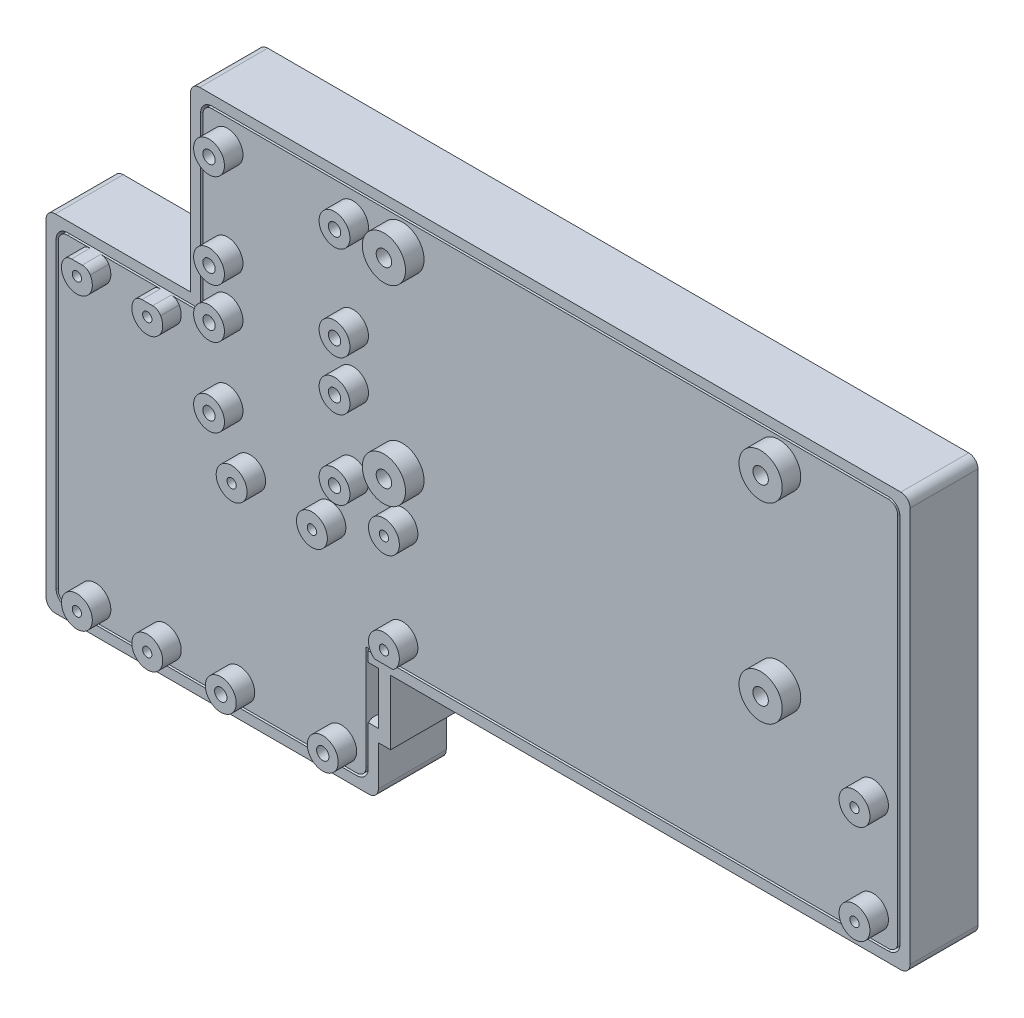
SolidWorks part; units mm, degrees
ref_plane "Front Plane" through (0, 0, 0) normal (0, 0, 1) x (1, 0, 0)
ref_plane "Top Plane" through (0, 0, 0) normal (0, 1, 0) x (1, 0, 0)
ref_plane "Right Plane" through (0, 0, 0) normal (1, 0, 0) x (0, 0, -1)
sketch "Sketch1" plane through (0, 0, 0) normal (0, 0, 1) x (1, 0, 0)
  line L0 (0, -14.35) -> (0, -44.85) construction
  line L1 (-8.255, -44.85) -> (8.255, -44.85) construction
  line L2 (-8.255, -44.85) -> (-8.255, -14.35) construction
  line L3 (-8.255, -14.35) -> (8.255, -14.35) construction
  line L4 (8.255, -44.85) -> (8.255, -14.35) construction
  line L5 (-8.255, -44.85) -> (8.255, -14.35) construction
  line L6 (-8.255, -14.35) -> (8.255, -44.85) construction
  line L7 (-10.16, 6.35) -> (10.16, 6.35) construction
  line L8 (-10.16, 6.35) -> (-10.16, -6.35) construction
  line L9 (-10.16, -6.35) -> (10.16, -6.35) construction
  line L10 (10.16, 6.35) -> (10.16, -6.35) construction
  line L11 (-10.16, 6.35) -> (10.16, -6.35) construction
  line L12 (-10.16, -6.35) -> (10.16, 6.35) construction
  line L13 (-10.16, 29.59) -> (10.16, 29.59) construction
  line L14 (-10.16, 29.59) -> (-10.16, 14.35) construction
  line L15 (-10.16, 14.35) -> (10.16, 14.35) construction
  line L16 (10.16, 29.59) -> (10.16, 14.35) construction
  line L17 (-10.16, 29.59) -> (10.16, 14.35) construction
  line L18 (-10.16, 14.35) -> (10.16, 29.59) construction
  line L19 (-20.16, 2.15) -> (-31.56, 2.15) construction
  line L20 (-20.16, 2.15) -> (-20.16, -44.85) construction
  line L21 (-20.16, -44.85) -> (-31.56, -44.85) construction
  line L22 (-31.56, 2.15) -> (-31.56, -44.85) construction
  line L23 (-20.16, 2.15) -> (-31.56, -44.85) construction
  line L24 (-20.16, -44.85) -> (-31.56, 2.15) construction
  line L25 (18.16, 29.59) -> (79.16, 29.59) construction
  line L26 (18.16, 29.59) -> (18.16, -1.41) construction
  line L27 (18.16, -1.41) -> (79.16, -1.41) construction
  line L28 (79.16, 29.59) -> (79.16, -1.41) construction
  line L29 (18.16, 29.59) -> (79.16, -1.41) construction
  line L30 (18.16, -1.41) -> (79.16, 29.59) construction
  line L31 (18.16, -9.41) -> (94.36, -9.41) construction
  line L32 (18.16, -9.41) -> (18.16, -25.41) construction
  line L33 (18.16, -25.41) -> (94.36, -25.41) construction
  line L34 (94.36, -9.41) -> (94.36, -25.41) construction
  line L35 (18.16, -9.41) -> (94.36, -25.41) construction
  line L36 (18.16, -25.41) -> (94.36, -9.41) construction
  line L37 (-37.56, 4.15) -> (-37.56, -47.85)
  line L38 (-37.56, -47.85) -> (12.255, -47.85)
  line L39 (12.255, -47.85) -> (12.255, -29.41)
  line L40 (12.255, -29.41) -> (98.36, -29.41)
  line L41 (98.36, -29.41) -> (98.36, 33.59)
  line L42 (98.36, 33.59) -> (-14.16, 33.59)
  line L43 (-14.16, 33.59) -> (-14.16, 4.15)
  line L44 (-14.16, 4.15) -> (-37.56, 4.15)
  line L45 (-39.56, 6.15) -> (-39.56, -49.85)
  line L46 (-39.56, -49.85) -> (14.255, -49.85)
  line L47 (14.255, -49.85) -> (14.255, -31.41)
  line L48 (14.255, -31.41) -> (100.36, -31.41)
  line L49 (100.36, -31.41) -> (100.36, 35.59)
  line L50 (100.36, 35.59) -> (-16.16, 35.59)
  line L51 (-16.16, 35.59) -> (-16.16, 6.15)
  line L52 (-16.16, 6.15) -> (-39.56, 6.15)
  line L53 (-35.56, 2.15) -> (-35.56, -45.85)
  line L54 (16.255, -31.41) -> (16.255, -41.85)
  line L55 (16.255, -41.85) -> (12.255, -41.85)
  line L56 (12.255, -39.85) -> (14.255, -39.85)
  line L57 (14.255, -31.41) -> (12.255, -31.41)
  line L58 (-35.56, -45.85) -> (10.255, -45.85)
  line L59 (13.255, -39.85) -> (13.255, -41.85) construction
  line L60 (10.255, -45.85) -> (10.255, -27.41)
  line L61 (10.255, -27.41) -> (96.36, -27.41)
  line L62 (96.36, -27.41) -> (96.36, 31.59)
  line L63 (96.36, 31.59) -> (-12.16, 31.59)
  line L64 (-12.16, 31.59) -> (-12.16, 2.15)
  line L65 (-12.16, 2.15) -> (-35.56, 2.15)
  line L66 (12.255, -39.85) -> (10.255, -39.85)
  line L67 (12.255, -31.41) -> (10.255, -31.41)
  circle A0 centre (-31.56, 2.15) radius 0.75
  circle A1 centre (-20.16, 2.15) radius 0.75
  circle A2 centre (-31.56, -44.85) radius 0.75
  circle A3 centre (-20.16, -44.85) radius 0.75
  circle A4 centre (-8.255, -44.85) radius 1
  circle A5 centre (8.255, -44.85) radius 1
  circle A8 centre (18.16, -25.41) radius 0.75
  circle A9 centre (18.16, -9.41) radius 0.75
  circle A10 centre (94.36, -9.41) radius 0.75
  circle A11 centre (94.36, -25.41) radius 0.75
  circle A12 centre (10.16, -6.35) radius 1
  circle A13 centre (-10.16, -6.35) radius 1
  circle A14 centre (-10.16, 6.35) radius 1
  circle A15 centre (10.16, 6.35) radius 1
  circle A16 centre (10.16, 14.35) radius 1
  circle A17 centre (10.16, 29.59) radius 1
  circle A18 centre (-10.16, 29.59) radius 1
  circle A19 centre (-10.16, 14.35) radius 1
  circle A20 centre (18.16, 29.59) radius 1.25
  circle A21 centre (18.16, -1.41) radius 1.25
  circle A22 centre (79.16, -1.41) radius 1.25
  circle A23 centre (79.16, 29.59) radius 1.25
  circle A24 centre (-6.5, -14.35) radius 0.75
  circle A25 centre (6.5, -14.35) radius 0.75
  circle A26 centre (8.255, -44.85) radius 2.5
  circle A27 centre (-8.255, -44.85) radius 2.5
  circle A28 centre (-6.5, -14.35) radius 2.5
  circle A29 centre (6.5, -14.35) radius 2.5
  circle A30 centre (10.16, -6.35) radius 2.5
  circle A31 centre (-10.16, -6.35) radius 2.5
  circle A32 centre (-10.16, 6.35) radius 2.5
  circle A33 centre (10.16, 6.35) radius 2.5
  circle A34 centre (-10.16, 14.35) radius 2.5
  circle A35 centre (10.16, 14.35) radius 2.5
  circle A36 centre (10.16, 29.59) radius 2.5
  circle A37 centre (-10.16, 29.59) radius 2.5
  circle A38 centre (-31.56, 2.15) radius 2.5
  circle A39 centre (-20.16, 2.15) radius 2.5
  circle A40 centre (-31.56, -44.85) radius 2.5
  circle A41 centre (-20.16, -44.85) radius 2.5
  circle A42 centre (18.16, 29.59) radius 3.5
  circle A43 centre (18.16, -1.41) radius 3.5
  circle A44 centre (79.16, 29.59) radius 3.5
  circle A45 centre (79.16, -1.41) radius 3.5
  circle A46 centre (18.16, -25.41) radius 2.5
  circle A47 centre (18.16, -9.41) radius 2.5
  circle A48 centre (94.36, -25.41) radius 2.5
  circle A49 centre (94.36, -9.41) radius 2.5
  point P0 (0, -29.6)
  point P5 (0, 0)
  point P10 (0, 21.97)
  point P15 (-25.86, -21.35)
  point P20 (48.66, 14.09)
  point P25 (56.26, -17.41)
  dimension "D4" = 2
  dimension "D9" = 1.5
  dimension "D21" = 2.5
  dimension "D30" = 5
  dimension "D31" = 5
  dimension "D32" = 7
  dimension "D33" = 5
  dimension "D1" = 16.51
  dimension "D2" = 20.32
  dimension "D3" = 12.7
  dimension "D5" = 15.24
  dimension "D6" = 20.32
  dimension "D7" = 47
  dimension "D8" = 11.4
  dimension "D10" = 13
  dimension "D11" = 30.5
  dimension "D12" = 16
  dimension "D13" = 76.2
  dimension "D14" = 31
  dimension "D15" = 61
  dimension "D16" = 8
  dimension "D17" = 8
  dimension "D18" = 8
  dimension "D19" = 8
  dimension "D20" = 10
  dimension "D22" = 6
  dimension "D23" = 2
  dimension "D24" = 4
  dimension "D25" = 4
  dimension "D26" = 4
  dimension "D27" = 4
  dimension "D28" = 4
  dimension "D29" = 3
  dimension "D35" = 2
  dimension "D36" = 6
  dimension "D34" = 2
  dimension "D37" = 2
extrude "base" add sketch "Sketch1" along normal blind 2 contours A49 L62 L63 A44 A42 A36 A37 L64 A34 A32 L65 A39 A38 L53 L58 A40 A41 A27 A26 L60 L61 A46 A48 A47 A45 A43 A35 A33 A31 A30 | A49 L62 A48 L61 A46 L60 L67 L39 L40 L41 L42 L43 L44 A39 L65 L64 A32 A34 A37 L63 A36 A42 A44 | A39 L44 A38 L65 | A41 L58 A40 L53 L65 A38 L44 L37 L38 L39 L66 L60 A26 A27 | A37 L63 L64 | L39 L67 L60 L66 | A48 L61 L62 region at (-35.31, 3.4299, 0) region at (-25.86, 3.1949, 0) region at (31.202, -3.3959, 0) region at (11.255, -35.63, 0) region at (-16.41, 2.8114, 0) region at (96.2013, -27.2513, 0) region at (-12.0013, 31.4313, 0)
extrude "pegs" add sketch "Sketch1<3>" along normal blind 5 contours L44 A38 A0 | L44 A39 A1 | A32 A14 | A31 A13 | A28 A24 | A29 A25 | A30 A12 | A37 A18 | A34 A19 | A36 A17 | A42 A20 | A35 A16 | A33 A15 | A43 A21 | A47 A9 | A46 A8 | A44 A23 | A45 A22 | A49 A10 | A48 A11 | A26 A5 | A27 A4 | A41 A3 | A40 A2 | L58 A40 | L58 A41 | L58 A27 | L58 A26 L60 | L61 A48 | L62 A48 | L62 A49 | L63 A44 | L63 A42 | L63 A36 | L64 A37 | L63 A37 | L64 A34 | L64 A32 | L65 A38 A0 | L65 A39 A1 region at (-31.56, 3.1466, 0) region at (-31.56, 1.0155, 0) region at (-20.16, 3.1466, 0) region at (-20.16, 1.0155, 0) region at (-32.0583, -42.4625, 0) region at (-31.56, -46.4687, 0) region at (8.6083, -46.1942, 0) region at (10.198, -44.6, 0) region at (-12.3618, 6.35, 0) region at (-12.0927, 6.35, 0) region at (-20.6583, -42.4625, 0) region at (-20.16, -46.4687, 0) region at (17.072, -23.2341, 0) region at (-8.255, -46.4687, 0) region at (-7.1094, -45.789, 0) region at (-12.3618, 14.35, 0) region at (-12.0927, 14.35, 0) region at (92.6372, -23.6872, 0) region at (94.36, -27.6118, 0) region at (96.5618, -25.41, 0) region at (-12.3618, 29.59, 0) region at (-12.0964, 29.59, 0) region at (91.9273, -9.41, 0) region at (96.5618, -9.41, 0) region at (-10.16, 31.7918, 0) region at (10.16, 31.7918, 0) region at (10.16, 31.5227, 0) region at (82.4144, 30.6114, 0) region at (79.16, 32.2026, 0) region at (18.16, 32.2026, 0) region at (18.16, 31.501, 0) region at (-8.9293, -14.35, 0) region at (4.0707, -14.35, 0) region at (7.7307, -6.35, 0) region at (-12.5893, -6.35, 0) region at (7.7307, 6.35, 0) region at (7.7307, 14.35, 0) region at (14.759, -1.41, 0) region at (75.759, -1.41, 0) region at (15.7307, -9.41, 0)
sketch "Sketch1<3>" plane through (0, 0, 0) normal (0, 0, 1) x (1, 0, 0) same geometry as "Sketch1"
fillet "Fillet1" radius 1.5 10 edges at (98.36, 33.59, 1) (98.36, -29.41, 1) (12.255, -47.85, 1) (-37.56, -47.85, 1) (-37.56, 4.15, 1) (-14.16, 33.59, 1) (-18.66, 4.15, 3.5) (-21.66, 4.15, 3.5) (-30.06, 4.15, 3.5) (-33.06, 4.15, 3.5)
extrude "Boss-Extrude1" add sketch "Sketch1<4>" against normal blind 9 and the other way up to surface (2 mm away) separate body contours L51 L52 L45 L46 L47 L48 L49 L50 A39 L44 L43 L42 L41 L40 L39 L38 L37 A38 | L44 A38 | L44 A39 | L55 L54 L48 L47 | L56 L39 L55 L47 region at (-39.1994, -21.85, 0) region at (-31.56, 4.3518, 0) region at (13.255, -40.85, 0) region at (-20.16, 4.3518, 0) region at (15.255, -36.63, 0) other way up to face at (96.86, -25.41, 2)
sketch "Sketch1<4>" plane through (0, 0, 0) normal (0, 0, 1) x (1, 0, 0) same geometry as "Sketch1"
extrude "Boss-Extrude2" add sketch "Sketch1<5>" along normal blind 2 from vertex contours L47 L57 L39 L56 | L56 L39 L55 L47 | L37 L38 L39 L40 L41 L42 L43 L44 region at (13.255, -40.85, 0) region at (13.255, -35.63, 0) starting at point (-37.56, 4.15, -9)
sketch "Sketch1<5>" plane through (0, 0, 0) normal (0, 0, 1) x (1, 0, 0) same geometry as "Sketch1"
extrude "Boss-Extrude3" add sketch "Sketch1<6>" along normal offset from surface (7 mm away) 2 from vertex contours A41 L58 A40 L53 L65 A38 L44 L37 L38 L39 L66 L60 A26 A27 | A39 L44 A38 L65 | L65 A38 L44 A0 | L65 A39 L44 A1 | A49 L62 A48 L61 A46 L60 L67 L39 L40 L41 L42 L43 L44 A39 L65 L64 A32 A34 A37 L63 A36 A42 A44 | L65 A1 | L65 A0 | L58 A40 | L58 A41 | L58 A27 | L58 A26 L60 | L64 A32 | L64 A34 | L64 A37 | L63 A37 | L63 A36 | L63 A42 | L63 A44 | L62 A49 | L62 A48 | L61 A48 | L61 A46 region at (-35.31, 3.4299, 0) region at (-31.56, 3.1466, 0) region at (-25.86, 3.1949, 0) region at (-20.16, 3.1466, 0) region at (-31.56, 2.4683, 0) region at (-16.41, 2.8114, 0) region at (-20.16, 2.4683, 0) region at (-31.56, -46.4687, 0) region at (8.6083, -46.1942, 0) region at (-12.3618, 6.35, 0) region at (-20.16, -46.4687, 0) region at (18.16, -27.6118, 0) region at (-8.255, -46.4687, 0) region at (-12.3618, 14.35, 0) region at (94.36, -27.6118, 0) region at (96.5618, -25.41, 0) region at (-12.3618, 29.59, 0) region at (96.5618, -9.41, 0) region at (-10.16, 31.7918, 0) region at (10.16, 31.7918, 0) region at (79.16, 32.2026, 0) region at (18.16, 32.2026, 0) up to face at (14.2342, -18.4633, 2) starting at point (-37.56, 4.15, -7)
sketch "Sketch1<6>" plane through (0, 0, 0) normal (0, 0, 1) x (1, 0, 0) same geometry as "Sketch1"
fillet "Fillet2" radius 1.5 12 edges at (14.255, -49.85, -3.5) (-39.56, -49.85, -3.5) (100.36, -31.41, -3.5) (100.36, 35.59, -3.5) (-16.16, 35.59, -3.5) (-39.56, 6.15, -3.5) (98.36, 33.59, 1) (98.36, -29.41, 1) (12.255, -47.85, 1) (-37.56, -47.85, 1) (-14.16, 33.59, 1) (-37.56, 4.15, 1)
chamfer "Chamfer1" distance 1 angle 20 15 edges at (12.255, -43.1, 2) (11.8157, -47.4107, 2) (-12.6525, -47.85, 2) (-37.1207, -47.4107, 2) (-37.56, -21.85, 2) (-37.1207, 3.7107, 2) (-25.11, 4.15, 2) (-14.16, 18.12, 2) (-13.7207, 33.1507, 2) (42.1, 33.59, 2) (97.9207, 33.1507, 2) (98.36, 2.09, 2) (97.9207, -28.9707, 2) (54.5575, -29.41, 2) (12.255, -30.41, 2) first distance on face at (12.255, -43.1, 1) first distance on face at (11.6603, -47.2553, 1) first distance on face at (-12.6525, -47.85, 1) first distance on face at (-36.9653, -47.2553, 1) first distance on face at (-37.56, -21.85, 1) first distance on face at (-36.9653, 3.5553, 1) first distance on face at (-25.11, 4.15, 1) first distance on face at (-14.16, 18.12, 1) first distance on face at (-13.5653, 32.9953, 1) first distance on face at (42.1, 33.59, 1) first distance on face at (97.7653, 32.9953, 1) first distance on face at (98.36, 2.09, 1) first distance on face at (97.7653, -28.8153, 1) first distance on face at (54.5575, -29.41, 1) first distance on face at (12.255, -30.41, 1)
